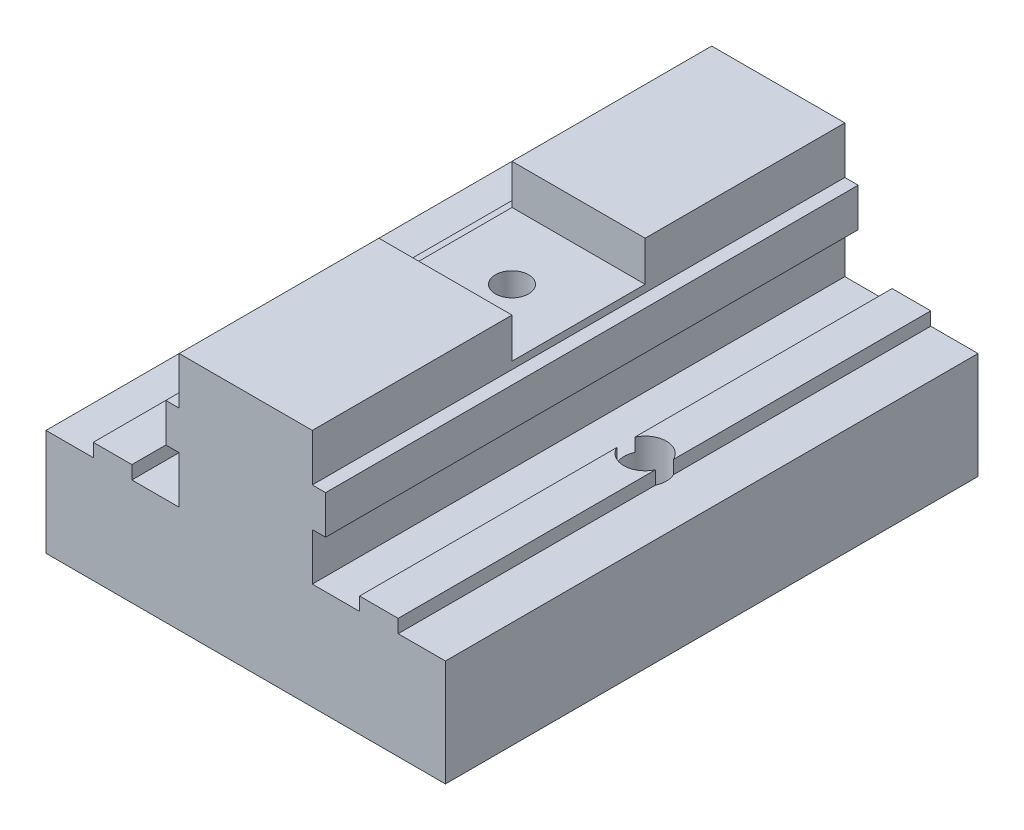
SolidWorks part; units mm, degrees
ref_plane "Front Plane" through (0, 0, 0) normal (0, 0, 1) x (1, 0, 0)
ref_plane "Top Plane" through (0, 0, 0) normal (0, 1, 0) x (1, 0, 0)
ref_plane "Right Plane" through (0, 0, 0) normal (1, 0, 0) x (0, 0, -1)
sketch "Esquisse1" plane through (0, 0, 0) normal (0, 0, 1) x (1, 0, 0)
  line L0 (-15, 0) -> (-15, 8)
  line L1 (-15, 8) -> (-11.45, 8)
  line L2 (-11.45, 8) -> (-11.45, 9)
  line L3 (-11.45, 9) -> (-8.55, 9)
  line L4 (-8.55, 9) -> (-8.55, 8)
  line L5 (-8.55, 8) -> (-5, 8)
  line L6 (-5, 8) -> (-5, 11.55)
  line L7 (0, 0) -> (-15, 0)
  line L8 (-5, 11.55) -> (-6, 11.55)
  line L9 (-6, 11.55) -> (-6, 14.45)
  line L10 (-6, 14.45) -> (-5, 14.45)
  line L11 (-5, 14.45) -> (-5, 18)
  line L12 (-5, 18) -> (0, 18)
  line L13 (0, 18) -> (0, 0)
  dimension "D1" = 15
  dimension "D2" = 8
  dimension "D3" = 1
  dimension "D4" = 2.9
  dimension "D5" = 3.55
  dimension "D6" = 5
  dimension "D7" = 10
  dimension "D8" = 2.9
  dimension "D9" = 3.55
extrude "Main" add sketch "Esquisse1" along normal blind 40
sketch "Esquisse2" plane through (0, 9, 0) normal (0, 1, 0) x (1, 0, 0)
  line L1 (-15, -40) -> (-15, 0) construction
  circle A1 centre (-10, -20) radius 1.6
  point P0 (-15, -20)
  dimension "D3" = 3.2
  dimension "D1" = 5
extrude "TopHole" cut sketch "Esquisse2" against normal through all
ref_axis "Axe1" through (-5.5, 0, 0) along (1, 0, 0)
mirror "Symétrie1" about plane through (0, 0, 0) normal (1, 0, 0) of "Main", "TopHole"
sketch "Esquisse3" plane through (0, 18, 0) normal (0, 1, 0) x (1, 0, 0)
  line L0 (0, -2.2) -> (0, 2.2) construction
  line L1 (15, -40) -> (15, 0) construction
  circle A1 centre (0, -20) radius 1.25
  point P0 (15, -20)
  dimension "D1" = 2.5
extrude "CentralHole" cut sketch "Esquisse3" against normal through all
ref_axis "Axe2" through (16.5, 0, 0) along (-1, 0, 0)
sketch "Sketch1" plane through (0, 0, 0) normal (0, -1, 0) x (-1, 0, 0)
  circle A0 centre (10, -20) radius 4.25
  circle A1 centre (-10, -20) radius 4.25
  dimension "D1" = 8.5
extrude "Cut-Extrude1" cut sketch "Sketch1" against normal blind 5
sketch "Sketch2" plane through (0, 18, 0) normal (0, 1, 0) x (1, 0, 0)
  line L0 (5, -40) -> (5, 0) construction
  line L1 (5, -15) -> (-5, -15)
  line L2 (5, -15) -> (5, -25)
  line L3 (5, -25) -> (-5, -25)
  line L4 (-5, -15) -> (-5, -25)
  line L5 (-5, -40) -> (-5, 0) construction
  line L6 (15, -40) -> (15, 0) construction
  point P8 (5, -20)
  point P9 (0, 0)
  point P10 (15, -20)
  point P11 (0, 0)
  dimension "D1" = 10
extrude "Cut-Extrude2" cut sketch "Sketch2" against normal blind 3
